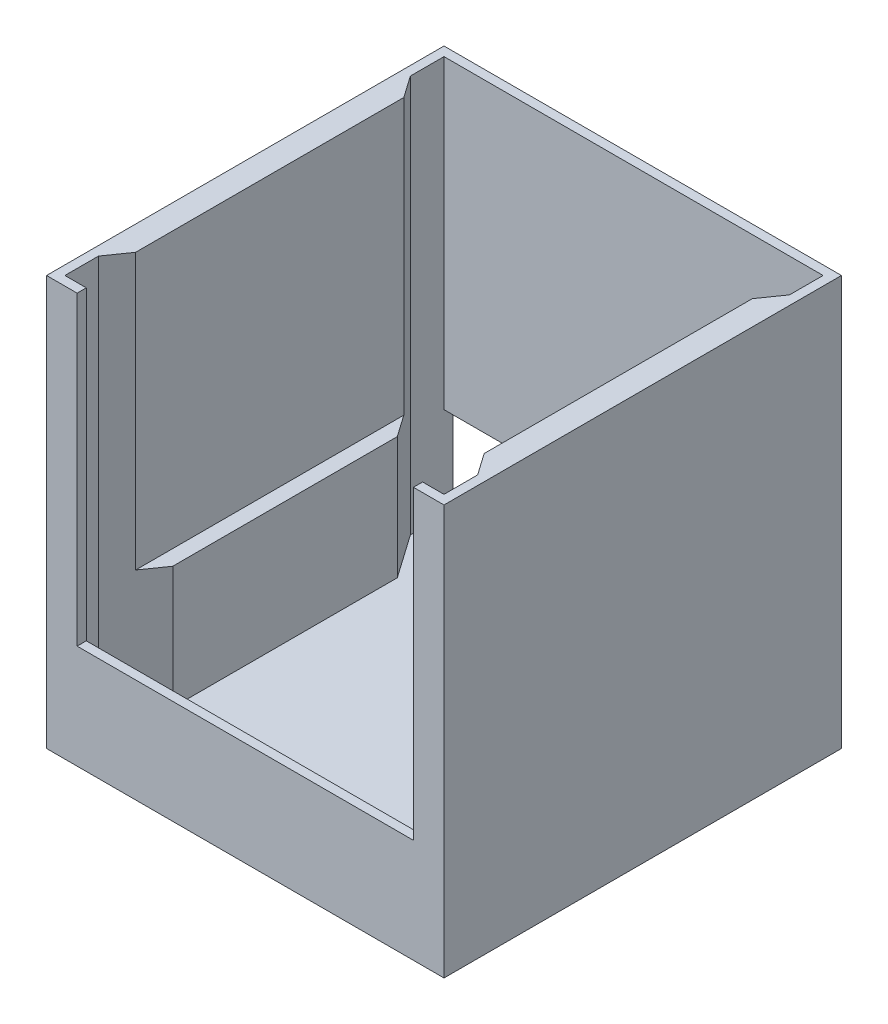
SolidWorks part; units mm, degrees
ref_plane "Front Plane" through (0, 0, 0) normal (0, 0, 1) x (1, 0, 0)
ref_plane "Top Plane" through (0, 0, 0) normal (0, 1, 0) x (1, 0, 0)
ref_plane "Right Plane" through (0, 0, 0) normal (1, 0, 0) x (0, 0, -1)
sketch "Sketch1" plane through (0, 0, 0) normal (0, 1, 0) x (1, 0, 0)
  line L0 (0, 82.55) -> (0, -127)
  line L1 (-82.55, -82.55) -> (82.55, -82.55)
  line L2 (-82.55, -82.55) -> (-82.55, 82.55)
  line L3 (-82.55, 82.55) -> (82.55, 82.55)
  line L4 (82.55, -82.55) -> (82.55, 82.55)
  line L5 (-82.55, -82.55) -> (82.55, 82.55) construction
  line L6 (-82.55, 82.55) -> (82.55, -82.55) construction
  line L7 (-78.74, -78.74) -> (78.74, -78.74)
  line L8 (-78.74, -78.74) -> (-78.74, 78.74)
  line L9 (-78.74, 78.74) -> (78.74, 78.74)
  line L10 (78.74, -78.74) -> (78.74, 78.74)
  line L11 (-78.74, -78.74) -> (78.74, 78.74) construction
  line L12 (-78.74, 78.74) -> (78.74, -78.74) construction
  line L13 (-78.74, 64.77) -> (-72.39, 64.77)
  line L14 (-78.74, 64.77) -> (-78.74, -64.77)
  line L15 (-78.74, -64.77) -> (-72.39, -64.77)
  line L16 (-72.39, 64.77) -> (-72.39, -64.77)
  line L17 (78.74, -64.77) -> (72.39, -64.77)
  line L18 (72.39, 64.77) -> (72.39, -64.77)
  line L19 (78.74, 64.77) -> (72.39, 64.77)
  line L20 (78.74, 64.77) -> (78.74, -64.77)
  point P0 (0, 0)
  point P6 (0, 0)
  point P21 (0, 0)
  dimension "D1" = 3.81
  dimension "D2" = 165.1
  dimension "D3" = 165.1
  dimension "D4" = 13.97
  dimension "D5" = 13.97
  dimension "D6" = 6.35
extrude "Boss-Extrude1" add sketch "Sketch1" along normal blind 127 contours L8 L9 L0 L3 L2 L1 L7 | L16 L13 L8 L15 | L10 L7 L0 L1 L4 L3 L9 | L10 L19 L18 L17 region at (41.275, 0, -80.7041) region at (-1.8459, 0, -80.645) region at (-75.565, 0, 0) region at (75.565, 0, 0)
sketch "Sketch4" plane through (0, 0, 0) normal (0, -1, 0) x (1, 0, 0)
  line L1 (-82.55, -82.55) -> (82.55, -82.55)
  line L2 (-82.55, -82.55) -> (-82.55, 82.55)
  line L3 (-82.55, 82.55) -> (82.55, 82.55)
  line L4 (82.55, -82.55) -> (82.55, 82.55)
  line L5 (78.74, 78.74) -> (-78.74, 78.74)
  line L6 (78.74, 78.74) -> (78.74, -78.74)
  line L7 (78.74, -78.74) -> (-78.74, -78.74)
  line L8 (-78.74, 78.74) -> (-78.74, -78.74)
  line L9 (-78.74, -78.74) -> (78.74, -78.74)
  line L10 (-78.74, -78.74) -> (-78.74, -82.55)
  line L11 (-78.74, -82.55) -> (78.74, -82.55)
  line L12 (78.74, -78.74) -> (78.74, -82.55)
  line M10 (-78.74, -78.74) -> (-78.74, -64.77)
  line M14 (-78.74, 64.77) -> (-78.74, 78.74)
  line M15 (-78.74, 78.74) -> (78.74, 78.74)
  line M16 (78.74, 78.74) -> (78.74, 64.77)
  line M20 (78.74, -64.77) -> (78.74, -78.74)
  line M21 (82.55, -82.55) -> (82.55, 82.55)
  line M22 (82.55, 82.55) -> (-82.55, 82.55)
  line M23 (-82.55, 82.55) -> (-82.55, -82.55)
  line M24 (-82.55, -82.55) -> (82.55, -82.55)
extrude "Boss-Extrude2" add sketch "Sketch4" along normal blind 38.1 contours L12 L10 L8 L6 M20 M24 M21 M22 M23 M10 M14 M15 M16 region at (-80.2151, 0, 0)
sketch "Sketch5" plane through (0, -38.1, 0) normal (0, -1, 0) x (1, 0, 0)
  line L1 (-82.55, 82.55) -> (82.55, 82.55)
  line L2 (-82.55, 82.55) -> (-82.55, -82.55)
  line L3 (-82.55, -82.55) -> (82.55, -82.55)
  line L4 (82.55, 82.55) -> (82.55, -82.55)
extrude "Boss-Extrude3" add sketch "Sketch5" along normal blind 5.08
sketch "Sketch6" plane through (0, 0, 82.55) normal (0, 0, 1) x (1, 0, 0)
  line L0 (-82.55, 0) -> (82.55, 0) construction
  line L1 (-69.85, 127) -> (69.85, 127)
  line L2 (-69.85, 127) -> (-69.85, 0)
  line L3 (-69.85, 0) -> (69.85, 0)
  line L4 (69.85, 127) -> (69.85, 0)
  line L5 (-82.55, 127) -> (82.55, 127) construction
  line L6 (-82.55, 127) -> (-82.55, -43.18) construction
  line L7 (82.55, 127) -> (82.55, -43.18) construction
  dimension "D1" = 0
  dimension "D2" = 12.7
  dimension "D3" = 12.7
extrude "Cut-Extrude1" cut sketch "Sketch6" against normal blind 12.7
extrude "Boss-Extrude5" add sketch "Sketch1<4>" against normal blind 41.656 contours L10 L19 L18 L17 | L16 L13 L8 L15 region at (-75.565, 0, 0) region at (75.565, 0, 0)
sketch "Sketch1<4>" plane through (0, 0, 0) normal (0, 1, 0) x (1, 0, 0) same geometry as "Sketch1"
sketch "Sketch8" plane through (0, -38.1, 0) normal (0, 1, 0) x (1, 0, 0)
  line L0 (-78.74, -64.77) -> (-72.39, -64.77) construction
  line L1 (-72.39, 64.77) -> (-66.04, 64.77)
  line L2 (-72.39, 64.77) -> (-72.39, -64.77)
  line L3 (-72.39, -64.77) -> (-66.04, -64.77)
  line L4 (-66.04, 64.77) -> (-66.04, -64.77)
  line L5 (0, 78.74) -> (0, -78.74)
  line L6 (-78.74, 78.74) -> (78.74, 78.74) construction
  line L7 (-78.74, -78.74) -> (78.74, -78.74) construction
  line L8 (72.39, -64.77) -> (66.04, -64.77)
  line L9 (66.04, 64.77) -> (66.04, -64.77)
  line L10 (72.39, 64.77) -> (66.04, 64.77)
  line L11 (72.39, 64.77) -> (72.39, -64.77)
  line M6 (-72.39, 64.77) -> (-72.39, -64.77)
  dimension "D1" = 0
  dimension "D2" = 6.35
extrude "Boss-Extrude6" add sketch "Sketch8" along normal blind 50.8 contours L4 L1 L3 M6 | L11 L8 L9 L10 region at (-69.215, -38.1, 0)
sketch "Sketch9" plane through (0, -38.1, 0) normal (0, 1, 0) x (1, 0, 0)
  line L0 (-78.74, 64.77) -> (-66.04, 46.6325)
  line L1 (-66.04, 64.77) -> (-66.04, -64.77) construction
  line L2 (-66.04, 0) -> (66.04, 0)
  line L3 (-66.04, 64.77) -> (-66.04, -64.77) construction
  line L4 (66.04, 64.77) -> (66.04, -64.77) construction
  line L5 (-78.74, 64.77) -> (-66.04, 64.77)
  line L6 (-66.04, 64.77) -> (-66.04, 46.6325)
  line L7 (-78.74, -64.77) -> (-66.04, -64.77)
  line L8 (-66.04, -64.77) -> (-66.04, -46.6325)
  line L9 (-78.74, -64.77) -> (-66.04, -46.6325)
  line L10 (0, 82.55) -> (0, -127)
  line L11 (78.74, -64.77) -> (66.04, -64.77)
  line L12 (66.04, -64.77) -> (66.04, -46.6325)
  line L13 (78.74, -64.77) -> (66.04, -46.6325)
  line L14 (66.04, 64.77) -> (66.04, 46.6325)
  line L15 (78.74, 64.77) -> (66.04, 64.77)
  line L16 (78.74, 64.77) -> (66.04, 46.6325)
  dimension "D1" = 35
extrude "Cut-Extrude2" cut sketch "Sketch9" along normal through all contours L8 L0 L9 | L8 L9 L7 | L14 L16 L15 | L11 L12 L13 region at (-70.2733, -38.1, -58.7242)
ref_plane "Plane12" through (0, 0, 0) normal (-1, 0, 0) x (0, 0, 1)
